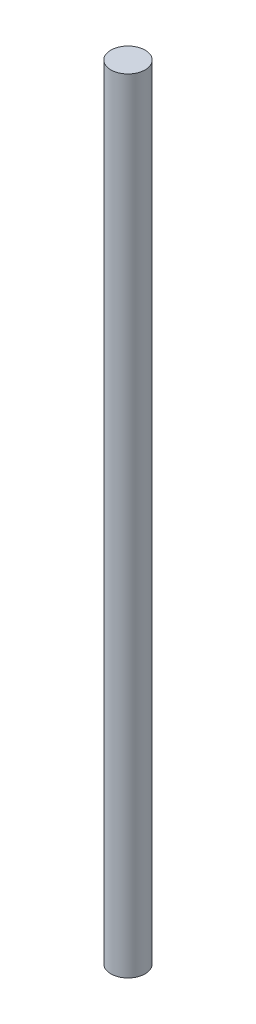
SolidWorks part; units mm, degrees
ref_plane "Front Plane" through (0, 0, 0) normal (0, 0, 1) x (1, 0, 0)
ref_plane "Top Plane" through (0, 0, 0) normal (0, 1, 0) x (1, 0, 0)
ref_plane "Right Plane" through (0, 0, 0) normal (1, 0, 0) x (0, 0, -1)
sketch "Sketch1" plane through (0, 0, 0) normal (0, 1, 0) x (1, 0, 0)
  circle A0 centre (0, 0) radius 2.5
  dimension "D1" = 5
extrude "Boss-Extrude1" add sketch "Sketch1" along normal blind 114.3
